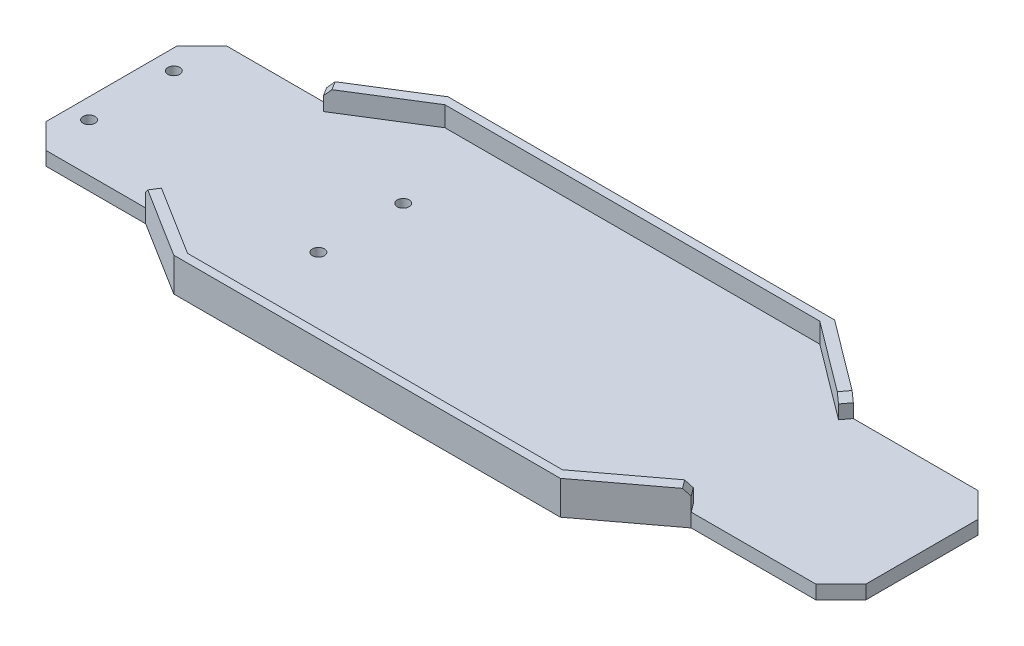
SolidWorks part; units mm, degrees
material "PETG - Polymaker"
ref_plane "Front Plane" through (0, 0, 0) normal (0, 0, 1) x (1, 0, 0)
ref_plane "Top Plane" through (0, 0, 0) normal (0, 1, 0) x (1, 0, 0)
ref_plane "Right Plane" through (0, 0, 0) normal (1, 0, 0) x (0, 0, -1)
sketch "Sketch1" plane through (0, 0, 0) normal (0, 1, 0) x (1, 0, 0)
  line L0 (-235.1499, 0) -> (235.1499, 0) construction
  line L1 (0, 0) -> (0, 52596.8311) construction
  line L2 (-107.5, 36.25) -> (-77.5, 55)
  line L3 (-77.5, 55) -> (77.5, 55)
  line L4 (-107.5, 36.25) -> (-157.5, 36.25)
  line L5 (-157.5, 36.25) -> (-157.5, -36.25)
  line L6 (-77.5, -55) -> (77.5, -55)
  line L7 (-107.5, -36.25) -> (-77.5, -55)
  line L8 (-107.5, -36.25) -> (-157.5, -36.25)
  line L9 (77.5, 55) -> (107.5, 32.5)
  line L10 (107.5, 32.5) -> (167.5, 32.5)
  line L11 (167.5, 32.5) -> (167.5, -32.5)
  line L12 (107.5, -32.5) -> (167.5, -32.5)
  line L13 (77.5, -55) -> (107.5, -32.5)
  point P3 (0, 0)
  point P10 (-92.5, 45.625)
  point P15 (-92.5, -45.625)
  point P18 (-157.5, 0)
  point P19 (0, -55)
  point P20 (0, 55)
  point P23 (167.5, 0)
  dimension "D1" = 55
  dimension "D2" = 72.5
  dimension "D3" = 30
  dimension "D4" = 50
  dimension "D5" = 155
  dimension "D6" = 60
  dimension "D7" = 65
  dimension "D8" = 30
  dimension "D9" = 110
extrude "Boss-Extrude1" add sketch "Sketch1" along normal blind 5.5
sketch "Sketch3" plane through (0, 5.5, 0) normal (0, 1, 0) x (1, 0, 0)
  line L0 (0, 0) -> (50000, 0) construction
  line L1 (0, 0) -> (0, 50000) construction
  line L2 (0, 55) -> (-77.5, 55)
  line L3 (77.5, 55) -> (-77.5, 55) construction
  line L4 (-77.5, 55) -> (-107.5, 36.25)
  line L5 (-107.5, 36.25) -> (-105.38, 32.858)
  line L6 (-105.38, 32.858) -> (-75.38, 51.608)
  line L7 (-75.38, 51.608) -> (0, 51.608)
  line L8 (-77.5, 55) -> (-75.38, 51.608) construction
  line L9 (0, 55) -> (77.5, 55)
  line L10 (77.5, 55) -> (107.5, 32.5)
  line L11 (107.5, 32.5) -> (104.956, 29.108)
  line L12 (104.956, 29.108) -> (74.956, 51.608)
  line L13 (74.956, 51.608) -> (0, 51.608)
  line L14 (74.956, 51.608) -> (77.5, 55) construction
  line L15 (74.956, -51.608) -> (77.5, -55) construction
  line L16 (-77.5, -55) -> (-75.38, -51.608) construction
  line L17 (74.956, -51.608) -> (0, -51.608)
  line L18 (104.956, -29.108) -> (74.956, -51.608)
  line L19 (107.5, -32.5) -> (104.956, -29.108)
  line L20 (77.5, -55) -> (107.5, -32.5)
  line L21 (0, -55) -> (77.5, -55)
  line L22 (-75.38, -51.608) -> (0, -51.608)
  line L23 (-105.38, -32.858) -> (-75.38, -51.608)
  line L24 (-107.5, -36.25) -> (-105.38, -32.858)
  line L25 (-77.5, -55) -> (-107.5, -36.25)
  line L26 (0, -55) -> (-77.5, -55)
  dimension "D1" = 4
extrude "Chassis-Walls1" add sketch "Sketch3" along normal blind 8
chamfer "Chamfer1" distance 10 angle 45 2 edges at (-157.5, 2.75, -36.25) (-157.5, 2.75, 36.25)
chamfer "Chamfer2" distance 10 angle 45 2 edges at (167.5, 2.75, -32.5) (167.5, 2.75, 32.5)
chamfer "Chamfer3" distance 2.5 angle 45 4 edges at (-106.44, 13.5, -34.554) (-106.44, 13.5, 34.554) (106.228, 13.5, 30.804) (106.228, 13.5, -30.804)
sketch "Sketch4" plane through (0, 0, 0) normal (0, -1, 0) x (1, 0, 0)
  line L0 (0, 0) -> (50000, 0) construction
  line L1 (-149.5, 17) -> (-57.5, 17) construction
  line L2 (-157.5, -26.25) -> (-157.5, 26.25) construction
  circle A0 centre (-149.5, 17) radius 2.4
  circle A1 centre (-57.5, 17) radius 2.4
  circle A2 centre (-57.5, -17) radius 2.4
  circle A3 centre (-149.5, -17) radius 2.4
  dimension "D1" = 4.8
  dimension "D2" = 4.8
  dimension "D3" = 8
  dimension "D4" = 92
  dimension "D5" = 34
extrude "Cut-Extrude1" cut sketch "Sketch4" against normal blind 10
